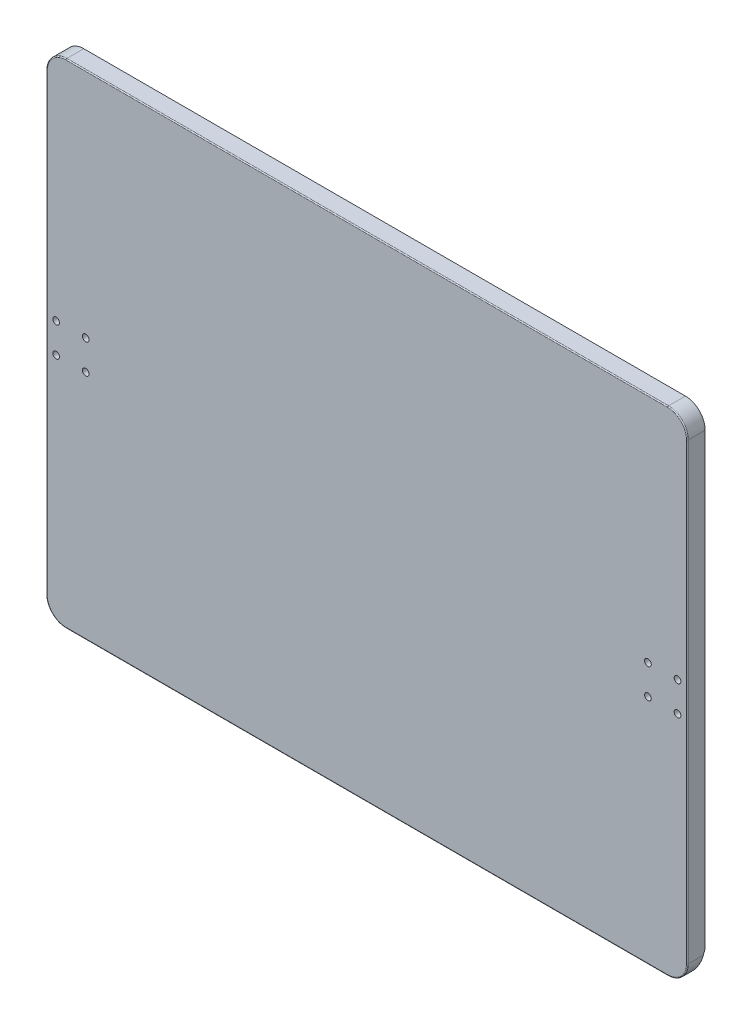
SolidWorks part; units mm, degrees
material "Beech"
ref_plane "Front Plane" through (0, 0, 0) normal (0, 0, 1) x (1, 0, 0)
ref_plane "Top Plane" through (0, 0, 0) normal (0, 1, 0) x (1, 0, 0)
ref_plane "Right Plane" through (0, 0, 0) normal (1, 0, 0) x (0, 0, -1)
sketch "Sketch1" plane through (0, 0, 0) normal (0, 0, 1) x (1, 0, 0)
  line L1 (0, 0) -> (650, 0)
  line L2 (0, 0) -> (0, 500)
  line L3 (0, 500) -> (650, 500)
  line L4 (650, 0) -> (650, 500)
  dimension "D1" = 500
  dimension "D2" = 650
extrude "base" add sketch "Sketch1" along normal blind 18
hole_wizard "counterbored M5 bolt holes" positions "Sketch2" profile "Sketch3" hole size "1/4" standard "ANSI Inch" end condition through all
sketch "Sketch2" plane through (0, 0, 18) normal (0, 0, 1) x (1, 0, 0)
  line L1 (10, 265) -> (40, 265)
  line L2 (10, 265) -> (10, 235)
  line L3 (10, 235) -> (40, 235)
  line L4 (40, 265) -> (40, 235)
  line L5 (10, 250) -> (0, 250)
  line L6 (0, 500) -> (0, 0) construction
  point P1 (10, 265)
  point P2 (40, 235)
  point P41 (10, 235)
  point P42 (40, 265)
  dimension "D1" = 30
  dimension "D2" = 30
  dimension "D3" = 10
sketch "Sketch3" plane through (10, 265, 18) normal (1, 0, 0) x (0, -1, 0)
  line L0 (0, 0) -> (0, 18)
  line L1 (0, 18) -> (3.3782, 18)
  line L2 (3.3782, 18) -> (3.3782, 0)
  line L5 (3.3782, 0) -> (0, 0)
  line L11 (0, -6.35) -> (0, 107.95) construction
  dimension "Thru Hole Dia." = 6.7564
  dimension "Thru Hole Depth" = 18
ref_plane "midplane in x" through (325, 0, 0) normal (-1, 0, 0) x (0, 0, 1)
mirror "mirror counterbored bolt holes" about plane through (325, 0, 0) normal (-1, 0, 0) of "counterbored M5 bolt holes"
fillet "round corners" radius 20 4 edges at (0, 500, 9) (650, 500, 9) (650, 0, 9) (0, 0, 9)
fillet "break top edge" radius 1 8 edges at (5.8579, 494.1421, 18) (325, 500, 18) (644.1421, 494.1421, 18) (650, 250, 18) (644.1421, 5.8579, 18) (325, 0, 18) (5.8579, 5.8579, 18) (0, 250, 18)
chamfer "front shadow chamfer" distance 25 angle 20 1 edges at (325, 0, 0) tangent propagation no first distance on face at (643.3782, 235, 0)
fillet "round chamfer edges" [suppressed] radius 1
equation "\"board_thickness\"= 18mm"
equation "\"way_width\"= 75mm"
equation "\"way_thickness\"= 50mm"
equation "\"radial_clearance\"= 0.1mm"
equation "\"slider_width\"= \"way_width\"-2* \"radial_clearance\""
equation "\"slider_thickness\"= \"way_thickness\" - 2 * \"radial_clearance\""
equation "\"column_width\"= \"way_width\" + 2 * \"board_thickness\""
equation "\"boxway_slot_width\"= 50mm"
equation "\"keeper_rail_width\"= (\"column_width\" - \"boxway_slot_width\")/2"
equation "\"slider_length\"= 125mm"
equation "\"nut_diameter\"= 22mm"
equation "\"nut_length\"= 15mm"
equation "\"leadscrew_diameter\"= 10mm"
equation "\"leadscrew_radial_clearance\"= 1mm"
equation "\"bearing_bolt_pattern_width\"= 30mm"
equation "\"bearing_bolt_pattern_height\"= 75mm"
equation "\"desktop_bolt_pattern_width\"= 30mm"
equation "\"desktop_bolt_pattern_height\"= 30mm"
equation "\"bearing_bolt_nut_counterbore_diameter\"= 12mm"
equation "\"bearing_bolt_nut_counterbore_depth\"= 10mm"
equation "\"desktop_depth\"= 500mm"
equation "\"desktop_width\"= 650mm"
equation "\"D1@Sketch1\"=\"desktop_depth\""
equation "\"D2@Sketch1\"=\"desktop_width\""
equation "\"desktop_thickness\"= 18mm"
equation "\"D1@base\" = \"desktop_thickness\""
equation "\"D1@Sketch2\"=\"desktop_bolt_pattern_height\""
equation "\"D2@Sketch2\"=\"desktop_bolt_pattern_width\""
